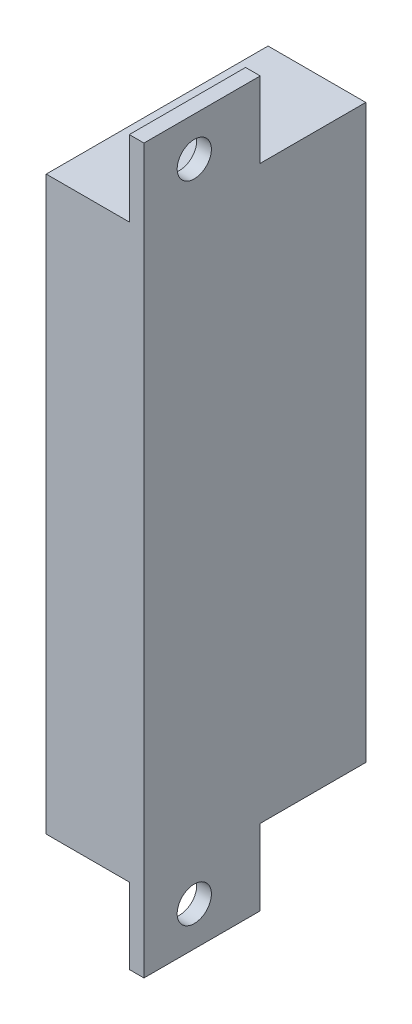
SolidWorks part; units mm, degrees
ref_plane "前视基准面" through (0, 0, 0) normal (0, 0, 1) x (1, 0, 0)
ref_plane "上视基准面" through (0, 0, 0) normal (0, 1, 0) x (1, 0, 0)
ref_plane "右视基准面" through (0, 0, 0) normal (1, 0, 0) x (0, 0, -1)
other "Configuration Table"
sketch "草图1" plane through (0, 0, 0) normal (0, 0, 1) x (1, 0, 0)
  line L1 (135, -110) -> (155, -110)
  line L2 (135, -110) -> (135, -30)
  line L3 (135, -30) -> (155, -30)
  line L4 (155, -110) -> (155, -30)
extrude "7423_enclosed_speaker_SIZE_VERIFY" [suppressed] add sketch "草图1" along normal blind 30 from offset 10
sketch "草图2" plane through (0, 0, 0) normal (0, 0, 1) x (1, 0, 0)
  line L1 (145, -102.25) -> (155, -102.25)
  line L2 (145, -102.25) -> (145, -43.75)
  line L3 (145, -43.75) -> (155, -43.75)
  line L4 (155, -102.25) -> (155, -43.75)
extrude "V09_Speaker_body58p5x22p7x10" add sketch "草图2" along normal blind 22.7 from offset 23.65
sketch "草图3" plane through (0, 0, 0) normal (0, 0, 1) x (1, 0, 0)
  line L1 (153.5, -110) -> (155, -110)
  line L2 (153.5, -110) -> (153.5, -102.25)
  line L3 (153.5, -102.25) -> (155, -102.25)
  line L4 (155, -110) -> (155, -102.25)
extrude "V09_Speaker_lower_ear" add sketch "草图3" along normal blind 11.9 from offset 34.45
sketch "草图4" plane through (0, 0, 0) normal (0, 0, 1) x (1, 0, 0)
  line L1 (153.5, -43.75) -> (155, -43.75)
  line L2 (153.5, -43.75) -> (153.5, -36)
  line L3 (153.5, -36) -> (155, -36)
  line L4 (155, -43.75) -> (155, -36)
extrude "V09_Speaker_upper_ear" add sketch "草图4" along normal blind 11.9 from offset 34.45
sketch "草图5" plane through (155, 0, 0) normal (1, 0, 0) x (0, 0, -1)
  circle A0 centre (-41.2, -106) radius 1.75
  circle A1 centre (-41.2, -40) radius 1.75
extrude "V09_Speaker_ear_D3p5_pitch66" cut sketch "草图5" against normal blind 1.5
